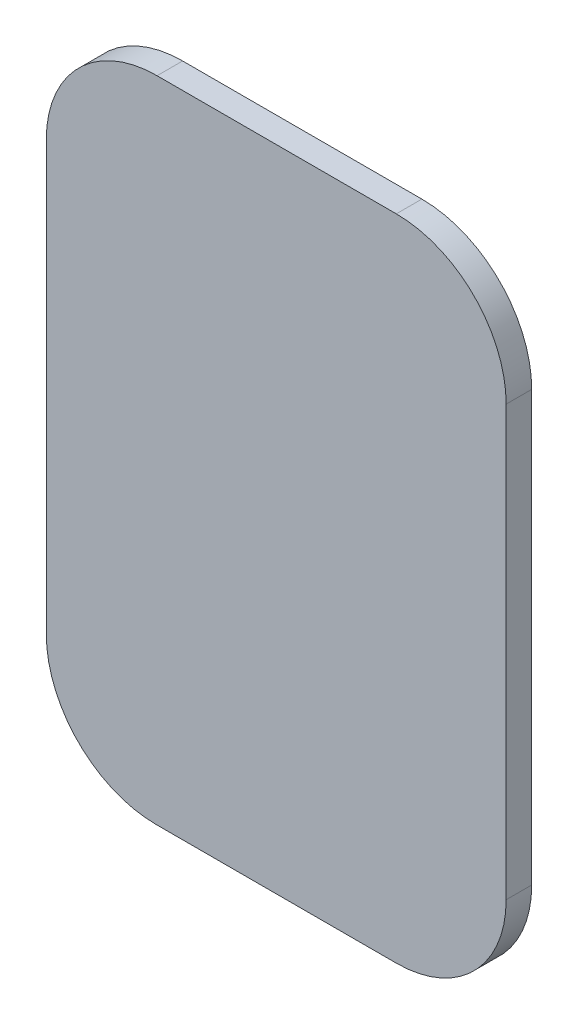
SolidWorks part; units mm, degrees
ref_plane "mating-plane" through (0, 0, 0) normal (0, 0, 1) x (1, 0, 0)
ref_plane "Top Plane" through (0, 0, 0) normal (0, 1, 0) x (1, 0, 0)
ref_plane "Right Plane" through (0, 0, 0) normal (1, 0, 0) x (0, 0, -1)
ref_axis "axis" through (0, 0, -0.4622) along (0, 0, 1)
sketch "Sketch9" plane through (0, 0, 0) normal (0, 0, 1) x (1, 0, 0)
  line L20 (0.9, 0.84) -> (0.9, -0.84)
  line L21 (0.47, -1.27) -> (-0.4698, -1.27)
  line L22 (0.9, -0.84) -> (0.47, -0.84) construction
  line L23 (0.47, -0.84) -> (0.47, -1.27) construction
  line L24 (0.9, -0.84) -> (0.9, -1.27) construction
  line L25 (0.9, -1.27) -> (0.47, -1.27) construction
  line L26 (-0.9, -0.8398) -> (-0.9, 0.8364)
  line L27 (0.9, -1.27) -> (-0.9, -1.27) construction
  line L28 (0.9, -1.27) -> (0.9, 1.27) construction
  line L29 (0.9, 1.27) -> (-0.9, 1.27) construction
  line L30 (-0.9, -1.27) -> (-0.9, 1.27) construction
  line L31 (-0.4664, 1.27) -> (0.47, 1.27)
  arc A1 (0.9, -0.84) -> (0.47, -1.27) centre (0.47, -0.84) cw
  arc A2 (-0.4698, -1.27) -> (-0.9, -0.8398) centre (-0.4698, -0.8398) cw
  arc A3 (-0.9, 0.8364) -> (-0.4664, 1.27) centre (-0.4664, 0.8364) cw
  arc A4 (0.47, 1.27) -> (0.9, 0.84) centre (0.47, 0.84) cw
extrude "landing-pad" add sketch "Sketch9" against normal blind 0.1 separate body
sketch "Sketch3" plane through (0, 0, 0) normal (0, 0, -1) x (-1, 0, 0)
  circle A0 centre (0, 0) radius 0.535
extrude "pin-body" [suppressed] add sketch "Sketch3" against normal blind 2.93 separate body
sketch "Sketch11" plane through (0, 0, 0) normal (0, 1, 0) x (1, 0, 0)
  line L0 (-0.005, 0) -> (-0.535, 0)
  line L2 (-0.535, 0) -> (-0.535, -0.53)
  arc A0 (-0.005, 0) -> (-0.535, -0.53) centre (-0.005, -0.53) ccw
revolve "dome" [suppressed] cut sketch "Sketch11" angle 360 about axis through (0, 0, -0.4622) along (0, 0, 1)
sketch "Sketch17" [suppressed] plane through (0, 0, 0) normal (0, 0, 1) x (1, 0, 0)
  line L1 (-7.7123, 1.2258) -> (6.7302, 1.2258)
  line L2 (-7.7123, 1.2258) -> (-7.7123, -1.8908)
  line L3 (-7.7123, -1.8908) -> (6.7302, -1.8908)
  line L4 (6.7302, 1.2258) -> (6.7302, -1.8908)
extrude "fake-thing" [suppressed] add sketch "Sketch17" along normal blind 0.7 separate body
sketch "Sketch8" [suppressed] plane through (0, 0, 0) normal (0, 0, -1) x (-1, 0, 0)
  circle A0 centre (0, 0) radius 0.749
  circle A1 centre (0, 0) radius 0.535
extrude "body-front" [suppressed] add sketch "Sketch8" against normal blind 3.81 from surface separate body starting at face at (0.0004, -0.0003, -0.1)
sketch "Sketch15" [suppressed] plane through (0, 0, 4.51) normal (0, 0, 1) x (1, 0, 0)
  circle A0 centre (0, 0) radius 0.535
extrude "plug" [suppressed] add sketch "Sketch15" against normal blind 0.75
sketch "Sketch13" [suppressed] plane through (0, 0, 4.51) normal (0, 0, 1) x (1, 0, 0)
  circle A1 centre (0, 0) radius 0.89
  circle A2 centre (0, 0) radius 0.749
extrude "body-back" [suppressed] add sketch "Sketch13" against normal blind 2
sketch "Sketch14" [suppressed] plane through (0, 0, 2.51) normal (0, 0, -1) x (-1, 0, 0)
  circle A0 centre (0, 0) radius 1.08
extrude "flange" [suppressed] add sketch "Sketch14" along normal blind 0.25
sketch "Sketch16" [suppressed] plane through (0, 0, 0) normal (1, 0, 0) x (0, 0, -1)
  line L5 (-2.26, -1.08) -> (-2.26, 1.08) construction
  line L6 (-2.26, -0.749) -> (-2.45, -0.749) construction
  line L7 (-2.45, -0.749) -> (-2.1, -0.749)
  line L8 (-2.45, -0.749) -> (-2.45, -0.814)
  line L9 (-2.45, -0.814) -> (-2.1, -0.749)
revolve "rib" [suppressed] add sketch "Sketch16" angle 360 about axis through (0, 0, -0.4622) along (0, 0, 1)
